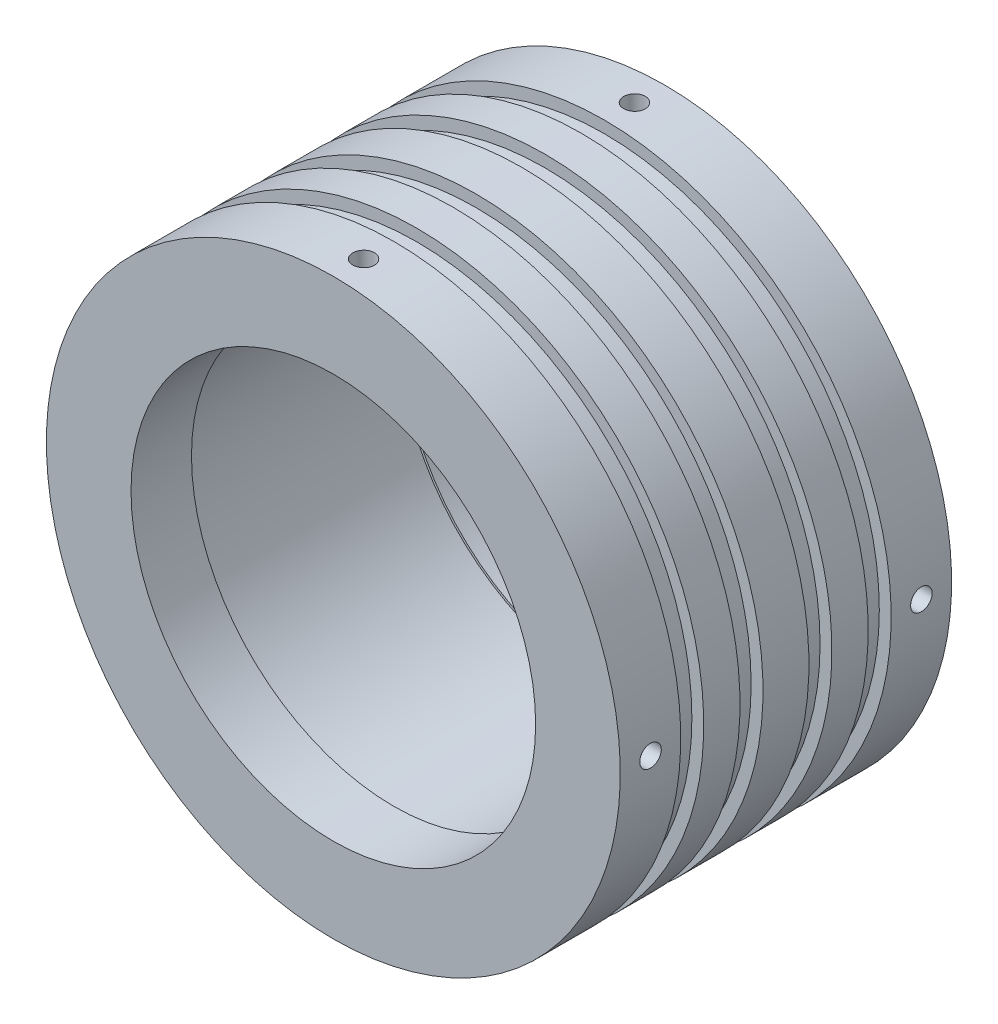
SolidWorks part; units mm, degrees
material "AISI 304"
ref_plane "XY" through (0, 0, 0) normal (0, 0, 1) x (1, 0, 0)
ref_plane "XZ" through (0, 0, 0) normal (0, 1, 0) x (1, 0, 0)
ref_plane "YZ" through (0, 0, 0) normal (1, 0, 0) x (0, 0, -1)
ref_axis "X" through (-31.7818, 0, 0) along (1, 0, 0)
ref_axis "Y" through (0, -31.7818, 0) along (0, 1, 0)
ref_axis "Z" through (0, 0, 19.1389) along (0, 0, -1)
sketch "Sketch2" plane through (0, 0, 0) normal (1, 0, 0) x (0, 0, -1)
  line L2 (-17.399, 30.1371) -> (-11.049, 30.1371)
  line L3 (-11.049, 30.1371) -> (-11.049, 28.8925)
  line L4 (-11.049, 28.8925) -> (-8.636, 28.8925)
  line L5 (-8.636, 28.8925) -> (-8.636, 30.1371)
  line L6 (-8.636, 30.1371) -> (-4.826, 30.1371)
  line L7 (-4.826, 30.1371) -> (-4.826, 28.8925)
  line L8 (-4.826, 28.8925) -> (-2.413, 28.8925)
  line L9 (-2.413, 28.8925) -> (-2.413, 30.1371)
  line L10 (-2.413, 30.1371) -> (0, 30.1371)
  line L11 (0, 30.1371) -> (0, 21.5011)
  line L12 (0, 21.5011) -> (-11.049, 21.5011)
  line L13 (-17.399, 30.1371) -> (-17.399, 21.2471)
  line L14 (-17.399, 21.2471) -> (-11.049, 21.2471)
  line L15 (-11.049, 21.2471) -> (-11.049, 21.5011)
  line L16 (0, 0) -> (-17.399, 0) construction
  line L17 (-17.399, 0) -> (-17.399, 21.2471) construction
  dimension "D1" = 8.636
  dimension "D3" = 2.413
  dimension "D4" = 3.81
  dimension "D5" = 2.413
  dimension "D6" = 8.89
  dimension "D7" = 6.35
  dimension "D8" = 30.1371
  dimension "D10" = 1.2446
revolve "Revolve1" add sketch "Sketch2" angle 360 about L16 other way angle 360
hole_wizard "#4-40 Tapped Hole1" positions "3DSketch1" profile "Sketch3" tap size "#4-40" standard "ANSI Inch"
sketch3d "3DSketch1"
  line L0 (0, 0, 0) -> (0, 0, 14.224)
  line L1 (0, 0, 14.224) -> (-30.1371, 0, 14.224)
  line L3 (30.1371, 0, 14.224) -> (0, -30.1371, 14.224)
  line L5 (0, -30.1371, 14.224) -> (-30.1371, 0, 14.224)
  line L9 (0, 0, 14.224) -> (0, -30.1371, 14.224)
  line L11 (0, 0, 14.224) -> (30.1371, 0, 14.224)
  line L13 (0, 0, 14.224) -> (0, 30.1371, 14.224)
  line L15 (0, -30.1371, 11.049) -> (0, -30.1371, 17.399)
  line L16 (0, 30.1371, 14.224) -> (-30.1371, 0, 14.224)
  line L18 (30.1371, 0, 14.224) -> (0, 30.1371, 14.224)
  circle A1 centre (0, 0, 11.049) radius 30.1371 construction
  circle A2 centre (0, 0, 17.399) radius 30.1371 construction
  point P5 (0, -30.1371, 14.224)
  point P7 (30.1371, 0, 14.224)
  point P20 (-30.1371, 0, 14.224)
  point P1370 (0, 0, -19.0881)
  point P1373 (0, 0, -12.7381)
  point P1390 (0, 30.1371, 14.224)
cosmetic thread "Hole Thread2" parameters "D1"=5.588, "D2"=2.8448
cosmetic thread "Hole Thread3" parameters "D1"=5.588, "D2"=2.8448
cosmetic thread "Hole Thread5" parameters "D1"=5.588, "D2"=2.8448
cosmetic thread "Hole Thread6" parameters "D1"=5.588, "D2"=2.8448
sketch "Sketch3" plane through (0, -30.1371, 14.224) normal (1, 0, 0) x (0, 0, -1)
  line L0 (0, 0) -> (0, 8.2992)
  line L1 (0, 8.2992) -> (1.1303, 7.62)
  line L2 (1.1303, 7.62) -> (1.1303, 0)
  line L5 (1.1303, 0) -> (0, 0)
  line L10 (0, 8.2992) -> (-1.1303, 7.62) construction
  line L11 (0, -6.35) -> (0, 107.95) construction
  dimension "Tap Drill Dia." = 2.2606
  dimension "Tap Drill Depth" = 7.62
  dimension "Drill Angle" = 118
sketch "Sketch4" plane through (0, 0, 17.399) normal (0, 0, 1) x (1, 0, 0)
  line L0 (-4.6416, 20.9941) -> (-1.5875, 17.94)
  line L1 (1.5875, 17.94) -> (4.6416, 20.9941)
  line L2 (0, 0) -> (0, 30.1371) construction
  line L3 (20.9941, 4.6416) -> (17.94, 1.5875)
  line L4 (17.94, -1.5875) -> (20.9941, -4.6416)
  line L5 (4.6416, -20.9941) -> (1.5875, -17.94)
  line L6 (-1.5875, -17.94) -> (-4.6416, -20.9941)
  line L7 (-20.9941, -4.6416) -> (-17.94, -1.5875)
  line L8 (-17.94, 1.5875) -> (-20.9941, 4.6416)
  line L10 (1.5875, 17.94) -> (0, 0) construction
  circle A1 centre (0, 0) radius 30.1371
  circle A2 centre (0, 0) radius 30.1371
  arc A3 (-17.94, 1.5875) -> (-17.94, -1.5875) centre (0, 0) ccw
  circle A4 centre (0, 0) radius 21.5011 construction
  arc A5 (-20.9941, -4.6416) -> (-4.6416, -20.9941) centre (0, 0) ccw
  arc A6 (1.5875, 17.94) -> (-1.5875, 17.94) centre (0, 0) ccw
  arc A7 (17.94, -1.5875) -> (17.94, 1.5875) centre (0, 0) ccw
  arc A8 (-1.5875, -17.94) -> (1.5875, -17.94) centre (0, 0) ccw
  arc A9 (-4.6416, 20.9941) -> (-20.9941, 4.6416) centre (0, 0) ccw
  arc A10 (20.9941, 4.6416) -> (4.6416, 20.9941) centre (0, 0) ccw
  arc A11 (4.6416, -20.9941) -> (20.9941, -4.6416) centre (0, 0) ccw
  dimension "D2" = 45
  dimension "D4" = 3.175
  dimension "D1" = 0
  dimension "D3" = 4
extrude "Cut-Extrude1" [suppressed] cut sketch "Sketch4" against normal through all flip side to cut
fillet "Fillet1" [suppressed] radius 7.62
mirror "Mirror1" about plane through (0, 30.1371, 0) normal (0, 0, -1) of bodies 103
cosmetic thread "Hole Thread7" parameters "D1"=5.588, "D2"=2.8448
cosmetic thread "Hole Thread8" parameters "D1"=5.588, "D2"=2.8448
cosmetic thread "Hole Thread9" parameters "D1"=5.588, "D2"=2.8448
cosmetic thread "Hole Thread10" parameters "D1"=5.588, "D2"=2.8448
